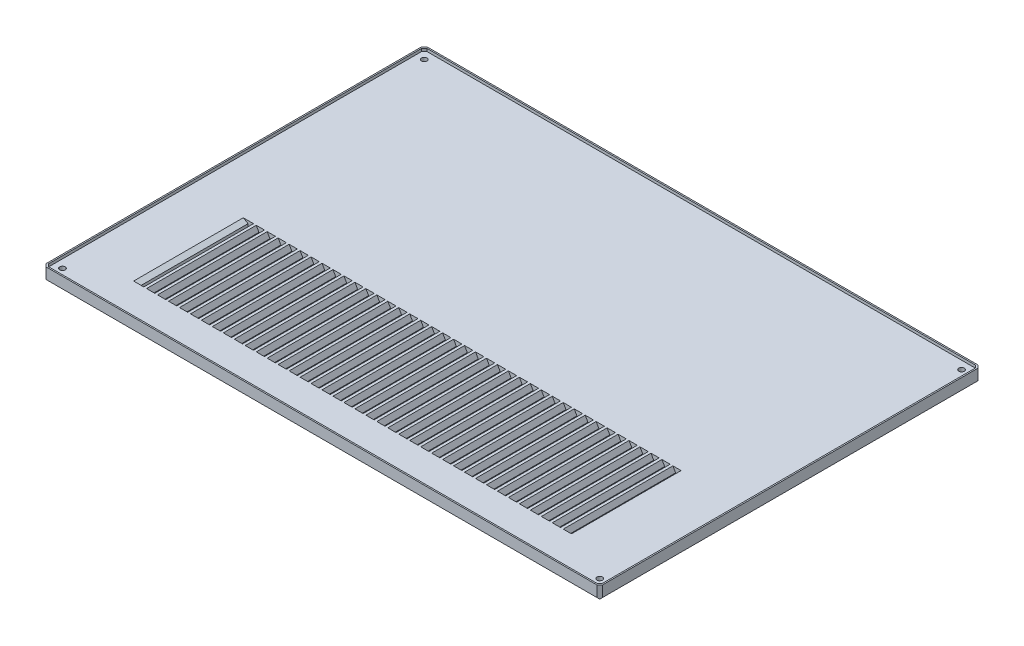
SolidWorks part; units mm, degrees
ref_plane "Płaszczyzna przednia" through (0, 0, 0) normal (0, 0, 1) x (1, 0, 0)
ref_plane "Płaszczyzna górna" through (0, 0, 0) normal (0, 1, 0) x (1, 0, 0)
ref_plane "Płaszczyzna prawa" through (0, 0, 0) normal (1, 0, 0) x (0, 0, -1)
sketch "Szkic1" plane through (0, 0, 0) normal (0, 1, 0) x (1, 0, 0)
  line L0 (-26.0061, 70.9107) -> (-26.0061, 74.9107)
  line L5 (-31.5061, 76.4107) -> (171.4939, 76.4107)
  line L10 (-31.5061, 76.4107) -> (-31.5061, -62.5893)
  line L11 (-31.5061, -62.5893) -> (171.4939, -62.5893)
  line L12 (171.4939, 76.4107) -> (171.4939, -62.5893)
  line L13 (-26.0061, 74.9107) -> (165.9939, 74.9107)
  line L14 (171.4939, -62.5893) -> (170.9939, -62.5893)
  line L15 (165.9939, 74.9107) -> (165.9939, 70.9107)
  line L16 (165.9939, 70.9107) -> (169.9939, 70.9107)
  line L17 (-31.0061, 75.9107) -> (170.9939, 75.9107)
  line L18 (-31.0061, 75.9107) -> (-31.0061, -62.0893)
  line L19 (-31.0061, -62.0893) -> (170.9939, -62.0893)
  line L20 (170.9939, 75.9107) -> (170.9939, -62.0893)
  line L21 (169.9939, 70.9107) -> (169.9939, -57.0893)
  line L22 (169.9939, -57.0893) -> (165.9939, -57.0893)
  line L23 (165.9939, -57.0893) -> (165.9939, -61.0893)
  line L24 (165.9939, -61.0893) -> (-26.0061, -61.0893)
  line L25 (-26.0061, -61.0893) -> (-26.0061, -57.0893)
  line L26 (-26.0061, -57.0893) -> (-30.0061, -57.0893)
  line L27 (-30.0061, -57.0893) -> (-30.0061, 70.9107)
  line L28 (-30.0061, 70.9107) -> (-26.0061, 70.9107)
  circle A0 centre (-28.0061, 72.9107) radius 1
  circle A1 centre (-28.0061, -59.0893) radius 1
  circle A2 centre (167.9939, -59.0893) radius 1
  circle A3 centre (167.9939, 72.9107) radius 1
extrude "Dodanie-wyciągnięcie2" add sketch "Szkic1" along normal blind 2 contours L12 L5 L10 L11 L17 L20 L19 L18 | L20 L17 L18 L19 A3 A2 A1 A0 L27 L28 L0 L13 L15 L16 L21 L22 L23 L24 L25 L26 | A0 | L28 L27 L26 L25 L24 L23 L22 L21 L16 L15 L13 L0 | A1 | A2 | A3
sketch "Szkic2" plane through (0, 2, 0) normal (0, 1, 0) x (1, 0, 0)
  line L0 (-26.0061, 70.9107) -> (-26.0061, 74.9107)
  line L5 (-31.5061, 76.4107) -> (171.4939, 76.4107)
  line L10 (-31.5061, 76.4107) -> (-31.5061, -62.5893)
  line L11 (-31.5061, -62.5893) -> (171.4939, -62.5893)
  line L12 (171.4939, 76.4107) -> (171.4939, -62.5893)
  line L13 (-26.0061, 74.9107) -> (165.9939, 74.9107)
  line L14 (171.4939, -62.5893) -> (170.9939, -62.5893)
  line L15 (165.9939, 74.9107) -> (165.9939, 70.9107)
  line L16 (165.9939, 70.9107) -> (169.9939, 70.9107)
  line L17 (-31.0061, 75.9107) -> (170.9939, 75.9107)
  line L18 (-31.0061, 75.9107) -> (-31.0061, -62.0893)
  line L19 (-31.0061, -62.0893) -> (170.9939, -62.0893)
  line L20 (170.9939, 75.9107) -> (170.9939, -62.0893)
  line L21 (169.9939, 70.9107) -> (169.9939, -57.0893)
  line L22 (169.9939, -57.0893) -> (165.9939, -57.0893)
  line L23 (165.9939, -57.0893) -> (165.9939, -61.0893)
  line L24 (165.9939, -61.0893) -> (-26.0061, -61.0893)
  line L25 (-26.0061, -61.0893) -> (-26.0061, -57.0893)
  line L26 (-26.0061, -57.0893) -> (-30.0061, -57.0893)
  line L27 (-30.0061, -57.0893) -> (-30.0061, 70.9107)
  line L28 (-30.0061, 70.9107) -> (-26.0061, 70.9107)
  circle A0 centre (-28.0061, 72.9107) radius 1
  circle A1 centre (-28.0061, -59.0893) radius 1
  circle A2 centre (167.9939, -59.0893) radius 1
  circle A3 centre (167.9939, 72.9107) radius 1
  line M57 (171.4939, -62.5893) -> (171.4939, 76.4107)
  line M58 (171.4939, 76.4107) -> (-31.5061, 76.4107)
  line M59 (-31.5061, 76.4107) -> (-31.5061, -62.5893)
  line M60 (-31.5061, -62.5893) -> (171.4939, -62.5893)
extrude "Dodanie-wyciągnięcie3" add sketch "Szkic2" along normal blind 1 contours L11 L17 L20 L19 L18 M60 M57 M58 M59
sketch "Szkic3" plane through (0, 2, 0) normal (0, 1, 0) x (1, 0, 0)
  line L1 (-31.0061, 75.9107) -> (170.9939, 75.9107) construction
  line L7 (-31.0061, -62.0893) -> (170.9939, -62.0893) construction
  line L12 (170.9939, 75.9107) -> (170.9939, -62.0893) construction
  line L14 (165.9939, -62.0893) -> (170.9939, -62.0893)
  line L15 (-31.0061, -62.0893) -> (170.9939, -62.0893) construction
  line L16 (170.9939, 75.9107) -> (170.9939, -62.0893) construction
  line L17 (170.9939, -62.0893) -> (170.9939, -57.0893)
  line L19 (170.9939, 70.9107) -> (170.9939, 75.9107)
  line L20 (-31.0061, 75.9107) -> (170.9939, 75.9107) construction
  line L21 (170.9939, 75.9107) -> (165.9939, 75.9107)
  circle A4 centre (-28.0061, 72.9107) radius 1
  circle A5 centre (-28.0061, -59.0893) radius 1
  circle A6 centre (167.9939, 72.9107) radius 1
  circle A7 centre (167.9939, -59.0893) radius 1
extrude "Wytnij-wyciągnięcie1" cut sketch "Szkic3" against normal blind 10
sketch "Szkic8" plane through (0, 0, 0) normal (0, -1, 0) x (1, 0, 0)
  line L1 (-31.5061, 62.5893) -> (171.4939, 62.5893)
  line L2 (-31.5061, 62.5893) -> (-31.5061, -76.4107)
  line L3 (-31.5061, -76.4107) -> (171.4939, -76.4107)
  line L4 (171.4939, 62.5893) -> (171.4939, -76.4107)
  circle A0 centre (-28.0061, 59.0893) radius 1
  circle A1 centre (-28.0061, -72.9107) radius 1
  circle A2 centre (167.9939, -72.9107) radius 1
  circle A3 centre (167.9939, 59.0893) radius 1
extrude "Dodanie-wyciągnięcie5" add sketch "Szkic8" along normal blind 2
sketch "Szkic9" plane through (0, -2, 0) normal (0, -1, 0) x (1, 0, 0)
  circle A0 centre (-28.0061, 59.0893) radius 2
  circle A1 centre (-28.0061, -72.9107) radius 2
  circle A2 centre (167.9939, -72.9107) radius 2
  circle A3 centre (167.9939, 59.0893) radius 2
extrude "Wytnij-wyciągnięcie4" cut sketch "Szkic9" against normal blind 1
chamfer "Sfazowanie1" distance 1 angle 45 4 edges at (171.4939, -2, -6.9107) (69.9939, -2, 62.5893) (-31.5061, -2, -6.9107) (69.9939, -2, -76.4107)
sketch "Szkic10" plane through (0, -2, 0) normal (0, -1, 0) x (1, 0, 0)
  line L0 (-5.2929, 50.1108) -> (-5.2929, 10.1108)
  line L1 (-9.2929, 40.3761) -> (-9.2929, 50.1108)
  line L2 (-9.2929, 50.1108) -> (-9.2929, 10.1108)
  line L3 (-9.2929, 10.1108) -> (-8.2929, 10.1108)
  line L4 (-8.2929, 10.1108) -> (-8.2929, 50.1108)
  line L5 (-8.2929, 50.1108) -> (-9.2929, 50.1108)
  line L6 (-5.2929, 10.1108) -> (-4.2929, 10.1108)
  line L7 (-4.2929, 10.1108) -> (-4.2929, 50.1108)
  line L8 (-4.2929, 50.1108) -> (-5.2929, 50.1108)
  line L9 (-1.2929, 50.1108) -> (-1.2929, 10.1108)
  line L10 (-1.2929, 10.1108) -> (-0.2929, 10.1108)
  line L11 (-0.2929, 10.1108) -> (-0.2929, 50.1108)
  line L12 (-0.2929, 50.1108) -> (-1.2929, 50.1108)
  line L13 (2.7071, 50.1108) -> (2.7071, 10.1108)
  line L14 (2.7071, 10.1108) -> (3.7071, 10.1108)
  line L15 (3.7071, 10.1108) -> (3.7071, 50.1108)
  line L16 (3.7071, 50.1108) -> (2.7071, 50.1108)
  line L17 (6.7071, 50.1108) -> (6.7071, 10.1108)
  line L18 (6.7071, 10.1108) -> (7.7071, 10.1108)
  line L19 (7.7071, 10.1108) -> (7.7071, 50.1108)
  line L20 (7.7071, 50.1108) -> (6.7071, 50.1108)
  line L21 (10.7071, 50.1108) -> (10.7071, 10.1108)
  line L22 (10.7071, 10.1108) -> (11.7071, 10.1108)
  line L23 (11.7071, 10.1108) -> (11.7071, 50.1108)
  line L24 (11.7071, 50.1108) -> (10.7071, 50.1108)
  line L25 (14.7071, 50.1108) -> (14.7071, 10.1108)
  line L26 (14.7071, 10.1108) -> (15.7071, 10.1108)
  line L27 (15.7071, 10.1108) -> (15.7071, 50.1108)
  line L28 (15.7071, 50.1108) -> (14.7071, 50.1108)
  line L29 (18.7071, 50.1108) -> (18.7071, 10.1108)
  line L30 (18.7071, 10.1108) -> (19.7071, 10.1108)
  line L31 (19.7071, 10.1108) -> (19.7071, 50.1108)
  line L32 (19.7071, 50.1108) -> (18.7071, 50.1108)
  line L33 (22.7071, 50.1108) -> (22.7071, 10.1108)
  line L34 (22.7071, 10.1108) -> (23.7071, 10.1108)
  line L35 (23.7071, 10.1108) -> (23.7071, 50.1108)
  line L36 (23.7071, 50.1108) -> (22.7071, 50.1108)
  line L37 (26.7071, 50.1108) -> (26.7071, 10.1108)
  line L38 (26.7071, 10.1108) -> (27.7071, 10.1108)
  line L39 (27.7071, 10.1108) -> (27.7071, 50.1108)
  line L40 (27.7071, 50.1108) -> (26.7071, 50.1108)
  line L41 (30.7071, 50.1108) -> (30.7071, 10.1108)
  line L42 (30.7071, 10.1108) -> (31.7071, 10.1108)
  line L43 (31.7071, 10.1108) -> (31.7071, 50.1108)
  line L44 (31.7071, 50.1108) -> (30.7071, 50.1108)
  line L45 (34.7071, 50.1108) -> (34.7071, 10.1108)
  line L46 (34.7071, 10.1108) -> (35.7071, 10.1108)
  line L47 (35.7071, 10.1108) -> (35.7071, 50.1108)
  line L48 (35.7071, 50.1108) -> (34.7071, 50.1108)
  line L49 (38.7071, 50.1108) -> (38.7071, 10.1108)
  line L50 (38.7071, 10.1108) -> (39.7071, 10.1108)
  line L51 (39.7071, 10.1108) -> (39.7071, 50.1108)
  line L52 (39.7071, 50.1108) -> (38.7071, 50.1108)
  line L53 (42.7071, 50.1108) -> (42.7071, 10.1108)
  line L54 (42.7071, 10.1108) -> (43.7071, 10.1108)
  line L55 (43.7071, 10.1108) -> (43.7071, 50.1108)
  line L56 (43.7071, 50.1108) -> (42.7071, 50.1108)
  line L57 (46.7071, 50.1108) -> (46.7071, 10.1108)
  line L58 (46.7071, 10.1108) -> (47.7071, 10.1108)
  line L59 (47.7071, 10.1108) -> (47.7071, 50.1108)
  line L60 (47.7071, 50.1108) -> (46.7071, 50.1108)
  line L61 (50.7071, 50.1108) -> (50.7071, 10.1108)
  line L62 (50.7071, 10.1108) -> (51.7071, 10.1108)
  line L63 (51.7071, 10.1108) -> (51.7071, 50.1108)
  line L64 (51.7071, 50.1108) -> (50.7071, 50.1108)
  line L65 (54.7071, 50.1108) -> (54.7071, 10.1108)
  line L66 (54.7071, 10.1108) -> (55.7071, 10.1108)
  line L67 (55.7071, 10.1108) -> (55.7071, 50.1108)
  line L68 (55.7071, 50.1108) -> (54.7071, 50.1108)
  line L69 (58.7071, 50.1108) -> (58.7071, 10.1108)
  line L70 (58.7071, 10.1108) -> (59.7071, 10.1108)
  line L71 (59.7071, 10.1108) -> (59.7071, 50.1108)
  line L72 (59.7071, 50.1108) -> (58.7071, 50.1108)
  line L73 (62.7071, 50.1108) -> (62.7071, 10.1108)
  line L74 (62.7071, 10.1108) -> (63.7071, 10.1108)
  line L75 (63.7071, 10.1108) -> (63.7071, 50.1108)
  line L76 (63.7071, 50.1108) -> (62.7071, 50.1108)
  line L77 (66.7071, 50.1108) -> (66.7071, 10.1108)
  line L78 (66.7071, 10.1108) -> (67.7071, 10.1108)
  line L79 (67.7071, 10.1108) -> (67.7071, 50.1108)
  line L80 (67.7071, 50.1108) -> (66.7071, 50.1108)
  line L81 (70.7071, 50.1108) -> (70.7071, 10.1108)
  line L82 (70.7071, 10.1108) -> (71.7071, 10.1108)
  line L83 (71.7071, 10.1108) -> (71.7071, 50.1108)
  line L84 (71.7071, 50.1108) -> (70.7071, 50.1108)
  line L85 (74.7071, 50.1108) -> (74.7071, 10.1108)
  line L86 (74.7071, 10.1108) -> (75.7071, 10.1108)
  line L87 (75.7071, 10.1108) -> (75.7071, 50.1108)
  line L88 (75.7071, 50.1108) -> (74.7071, 50.1108)
  line L89 (78.7071, 50.1108) -> (78.7071, 10.1108)
  line L90 (78.7071, 10.1108) -> (79.7071, 10.1108)
  line L91 (79.7071, 10.1108) -> (79.7071, 50.1108)
  line L92 (79.7071, 50.1108) -> (78.7071, 50.1108)
  line L93 (82.7071, 50.1108) -> (82.7071, 10.1108)
  line L94 (82.7071, 10.1108) -> (83.7071, 10.1108)
  line L95 (83.7071, 10.1108) -> (83.7071, 50.1108)
  line L96 (83.7071, 50.1108) -> (82.7071, 50.1108)
  line L97 (86.7071, 50.1108) -> (86.7071, 10.1108)
  line L98 (86.7071, 10.1108) -> (87.7071, 10.1108)
  line L99 (87.7071, 10.1108) -> (87.7071, 50.1108)
  line L100 (87.7071, 50.1108) -> (86.7071, 50.1108)
  line L101 (90.7071, 50.1108) -> (90.7071, 10.1108)
  line L102 (90.7071, 10.1108) -> (91.7071, 10.1108)
  line L103 (91.7071, 10.1108) -> (91.7071, 50.1108)
  line L104 (91.7071, 50.1108) -> (90.7071, 50.1108)
  line L105 (94.7071, 50.1108) -> (94.7071, 10.1108)
  line L106 (94.7071, 10.1108) -> (95.7071, 10.1108)
  line L107 (95.7071, 10.1108) -> (95.7071, 50.1108)
  line L108 (95.7071, 50.1108) -> (94.7071, 50.1108)
  line L109 (98.7071, 50.1108) -> (98.7071, 10.1108)
  line L110 (98.7071, 10.1108) -> (99.7071, 10.1108)
  line L111 (99.7071, 10.1108) -> (99.7071, 50.1108)
  line L112 (99.7071, 50.1108) -> (98.7071, 50.1108)
  line L113 (102.7071, 50.1108) -> (102.7071, 10.1108)
  line L114 (102.7071, 10.1108) -> (103.7071, 10.1108)
  line L115 (103.7071, 10.1108) -> (103.7071, 50.1108)
  line L116 (103.7071, 50.1108) -> (102.7071, 50.1108)
  line L117 (106.7071, 50.1108) -> (106.7071, 10.1108)
  line L118 (106.7071, 10.1108) -> (107.7071, 10.1108)
  line L119 (107.7071, 10.1108) -> (107.7071, 50.1108)
  line L120 (107.7071, 50.1108) -> (106.7071, 50.1108)
  line L121 (110.7071, 50.1108) -> (110.7071, 10.1108)
  line L122 (110.7071, 10.1108) -> (111.7071, 10.1108)
  line L123 (111.7071, 10.1108) -> (111.7071, 50.1108)
  line L124 (111.7071, 50.1108) -> (110.7071, 50.1108)
  line L125 (114.7071, 50.1108) -> (114.7071, 10.1108)
  line L126 (114.7071, 10.1108) -> (115.7071, 10.1108)
  line L127 (115.7071, 10.1108) -> (115.7071, 50.1108)
  line L128 (115.7071, 50.1108) -> (114.7071, 50.1108)
  line L129 (118.7071, 50.1108) -> (118.7071, 10.1108)
  line L130 (118.7071, 10.1108) -> (119.7071, 10.1108)
  line L131 (119.7071, 10.1108) -> (119.7071, 50.1108)
  line L132 (119.7071, 50.1108) -> (118.7071, 50.1108)
  line L133 (122.7071, 50.1108) -> (122.7071, 10.1108)
  line L134 (122.7071, 10.1108) -> (123.7071, 10.1108)
  line L135 (123.7071, 10.1108) -> (123.7071, 50.1108)
  line L136 (123.7071, 50.1108) -> (122.7071, 50.1108)
  line L137 (126.7071, 50.1108) -> (126.7071, 10.1108)
  line L138 (126.7071, 10.1108) -> (127.7071, 10.1108)
  line L139 (127.7071, 10.1108) -> (127.7071, 50.1108)
  line L140 (127.7071, 50.1108) -> (126.7071, 50.1108)
  line L141 (130.7071, 50.1108) -> (130.7071, 10.1108)
  line L142 (130.7071, 10.1108) -> (131.7071, 10.1108)
  line L143 (131.7071, 10.1108) -> (131.7071, 50.1108)
  line L144 (131.7071, 50.1108) -> (130.7071, 50.1108)
  line L145 (134.7071, 50.1108) -> (134.7071, 10.1108)
  line L146 (134.7071, 10.1108) -> (135.7071, 10.1108)
  line L147 (135.7071, 10.1108) -> (135.7071, 50.1108)
  line L148 (135.7071, 50.1108) -> (134.7071, 50.1108)
  line L149 (138.7071, 50.1108) -> (138.7071, 10.1108)
  line L150 (138.7071, 10.1108) -> (139.7071, 10.1108)
  line L151 (139.7071, 10.1108) -> (139.7071, 50.1108)
  line L152 (139.7071, 50.1108) -> (138.7071, 50.1108)
  line L153 (142.7071, 50.1108) -> (142.7071, 10.1108)
  line L154 (142.7071, 10.1108) -> (143.7071, 10.1108)
  line L155 (143.7071, 10.1108) -> (143.7071, 50.1108)
  line L156 (143.7071, 50.1108) -> (142.7071, 50.1108)
  line L157 (146.7071, 50.1108) -> (146.7071, 10.1108)
  line L158 (146.7071, 10.1108) -> (147.7071, 10.1108)
  line L159 (147.7071, 10.1108) -> (147.7071, 50.1108)
  line L160 (147.7071, 50.1108) -> (146.7071, 50.1108)
  dimension "D1" = 40
extrude "Wytnij-wyciągnięcie5" cut sketch "Szkic10" against normal blind 6 contours L4 L5 L1 L2 L3 | L7 L8 L0 L6 | L11 L12 L9 L10 | L27 L28 L25 L26 | L31 L32 L29 L30 | L35 L36 L33 L34 | L39 L40 L37 L38 | L43 L44 L41 L42 | L47 L48 L45 L46 | L51 L52 L49 L50 | L55 L56 L53 L54 | L59 L60 L57 L58 | L63 L64 L61 L62 | L67 L68 L65 L66 | L71 L72 L69 L70 | L75 L76 L73 L74 | L79 L80 L77 L78 | L83 L84 L81 L82 | L87 L88 L85 L86 | L91 L92 L89 L90 | L95 L96 L93 L94 | L99 L100 L97 L98 | L103 L104 L101 L102 | L107 L108 L105 L106 | L111 L112 L109 L110 | L115 L116 L113 L114 | L119 L120 L117 L118 | L123 L124 L121 L122 | L127 L128 L125 L126 | L131 L132 L129 L130 | L135 L136 L133 L134 | L139 L140 L137 L138 | L143 L144 L141 L142 | L147 L148 L145 L146 | L151 L152 L149 L150 | L155 L156 L153 L154 | L159 L160 L157 L158 | L13 L14 L15 L16 | L17 L18 L19 L20 | L21 L22 L23 L24
chamfer "Sfazowanie2" distance 1 angle 45 4 edges at (-31.5061, 1, 62.5893) (-31.5061, 1, -76.4107) (171.4939, 1, -76.4107) (171.4939, 1, 62.5893)
chamfer "Sfazowanie3" distance 1 angle 60 80 edges at (147.7071, 2, 30.1108) (146.7071, 2, 30.1108) (143.7071, 2, 30.1108) (142.7071, 2, 30.1108) (139.7071, 2, 30.1108) (138.7071, 2, 30.1108) (135.7071, 2, 30.1108) (134.7071, 2, 30.1108) (131.7071, 2, 30.1108) (130.7071, 2, 30.1108) (127.7071, 2, 30.1108) (126.7071, 2, 30.1108) (123.7071, 2, 30.1108) (122.7071, 2, 30.1108) (119.7071, 2, 30.1108) (118.7071, 2, 30.1108) (115.7071, 2, 30.1108) (114.7071, 2, 30.1108) (111.7071, 2, 30.1108) (110.7071, 2, 30.1108) (107.7071, 2, 30.1108) (106.7071, 2, 30.1108) (103.7071, 2, 30.1108) (102.7071, 2, 30.1108) (99.7071, 2, 30.1108) (98.7071, 2, 30.1108) (95.7071, 2, 30.1108) (94.7071, 2, 30.1108) (91.7071, 2, 30.1108) (90.7071, 2, 30.1108) (87.7071, 2, 30.1108) (86.7071, 2, 30.1108) (83.7071, 2, 30.1108) (82.7071, 2, 30.1108) (79.7071, 2, 30.1108) (78.7071, 2, 30.1108) (70.7071, 2, 30.1108) (75.7071, 2, 30.1108) (74.7071, 2, 30.1108) (71.7071, 2, 30.1108) (67.7071, 2, 30.1108) (66.7071, 2, 30.1108) (63.7071, 2, 30.1108) (62.7071, 2, 30.1108) (59.7071, 2, 30.1108) (58.7071, 2, 30.1108) (55.7071, 2, 30.1108) (54.7071, 2, 30.1108) (51.7071, 2, 30.1108) (50.7071, 2, 30.1108) (47.7071, 2, 30.1108) (46.7071, 2, 30.1108) (43.7071, 2, 30.1108) (42.7071, 2, 30.1108) (39.7071, 2, 30.1108) (38.7071, 2, 30.1108) (35.7071, 2, 30.1108) (34.7071, 2, 30.1108) (31.7071, 2, 30.1108) (30.7071, 2, 30.1108) (27.7071, 2, 30.1108) (26.7071, 2, 30.1108) (23.7071, 2, 30.1108) (22.7071, 2, 30.1108) (19.7071, 2, 30.1108) (18.7071, 2, 30.1108) (15.7071, 2, 30.1108) (14.7071, 2, 30.1108) (11.7071, 2, 30.1108) (10.7071, 2, 30.1108) (7.7071, 2, 30.1108) (6.7071, 2, 30.1108) (2.7071, 2, 30.1108) (3.7071, 2, 30.1108) (-1.2929, 2, 30.1108) (-0.2929, 2, 30.1108) (-4.2929, 2, 30.1108) (-5.2929, 2, 30.1108) (-8.2929, 2, 30.1108) (-9.2929, 2, 30.1108)
sketch "Szkic11" plane through (0, 3, 0) normal (0, 1, 0) x (1, 0, 0)
  line L3 (170.9939, 75.9107) -> (-31.0061, 75.9107)
  line L4 (69.9939, 75.9107) -> (69.9939, -62.0893)
  line L11 (-31.0061, -62.0893) -> (-31.0061, -61.0893)
  line L13 (-30.0061, -62.0893) -> (-31.0061, -62.0893)
  line L21 (-31.0061, -62.0893) -> (170.9939, -62.0893) construction
  line L34 (170.9939, 75.9107) -> (170.9939, -62.0893) construction
  line L35 (170.9939, -61.0893) -> (169.9939, -62.0893)
  line L36 (169.9939, -62.0893) -> (170.9939, -62.0893)
  line L37 (170.9939, -62.0893) -> (170.9939, -61.0893)
  line L38 (170.9939, 74.9107) -> (169.9939, 75.9107)
  line L39 (169.9939, 75.9107) -> (170.9939, 75.9107)
  line L40 (170.9939, 74.9107) -> (170.9939, 75.9107)
  line L41 (-31.0061, -61.0893) -> (-30.0061, -62.0893)
  line L42 (-30.0061, 75.9107) -> (-31.0061, 75.9107)
  line L43 (-31.0061, 74.9107) -> (-30.0061, 75.9107)
  line L44 (-31.0061, 74.9107) -> (-31.0061, 75.9107)
  line M20 (170.9939, 75.9107) -> (170.9939, -62.0893)
extrude "Dodanie-wyciągnięcie7" add sketch "Szkic11" along direction (0, 1, 0) on the side against the normal blind 3 contours L44 L43 L3 | L41 L11 L13 | L35 L36 M20 | L38 L3 M20
equation "\"`1\"=1"
